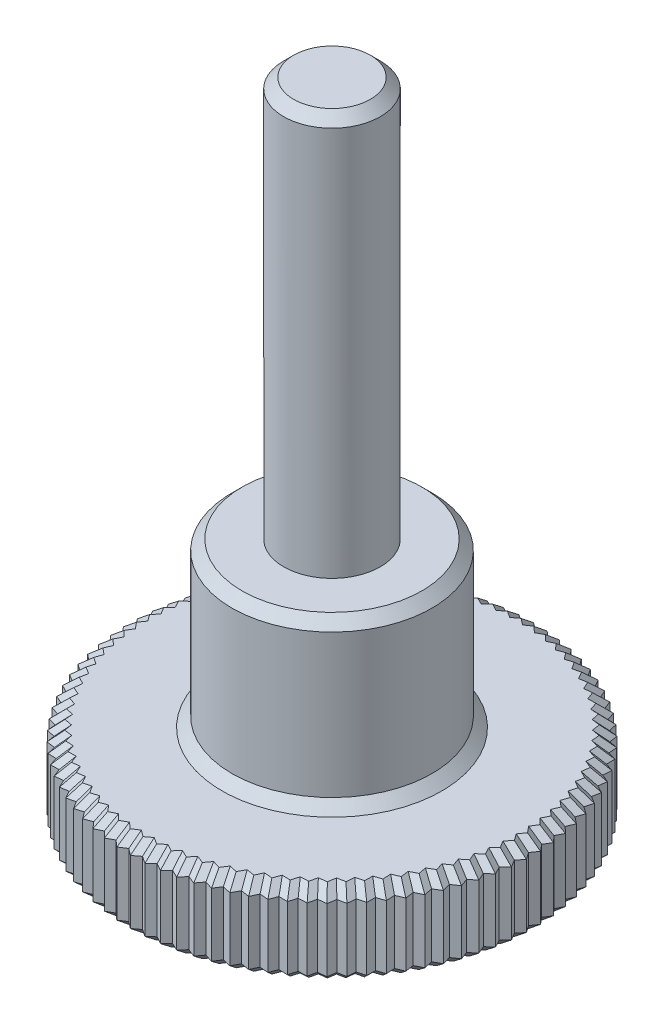
SolidWorks part; units mm, degrees
material "AISI 1020"
ref_plane "Front Plane" through (0, 0, 0) normal (0, 0, 1) x (1, 0, 0)
ref_plane "Top Plane" through (0, 0, 0) normal (0, 1, 0) x (1, 0, 0)
ref_plane "Right Plane" through (0, 0, 0) normal (1, 0, 0) x (0, 0, -1)
sketch "Sketch1" plane through (0, 0, 0) normal (0, 1, 0) x (1, 0, 0)
  line L0 (0, 0) -> (0, 6.05) construction
  line L1 (0, 6.05) -> (0.2058, 5.8938)
  line L2 (0.422, 6.0353) -> (0.2058, 5.8938)
  line L3 (0.2111, 6.0463) -> (0, 0) construction
  line L4 (0.422, 6.0353) -> (0.6164, 5.8651)
  line L5 (0.842, 5.9911) -> (0.6164, 5.8651)
  line L6 (0.842, 5.9911) -> (1.0241, 5.8078)
  line L7 (1.2579, 5.9178) -> (1.0241, 5.8078)
  line L8 (1.2579, 5.9178) -> (1.4267, 5.7222)
  line L9 (1.6676, 5.8156) -> (1.4267, 5.7222)
  line L10 (1.6676, 5.8156) -> (1.8224, 5.6088)
  line L11 (2.0692, 5.6851) -> (1.8224, 5.6088)
  line L12 (2.0692, 5.6851) -> (2.2092, 5.468)
  line L13 (2.4608, 5.527) -> (2.2092, 5.468)
  line L14 (2.4608, 5.527) -> (2.5852, 5.3005)
  line L15 (2.8403, 5.3418) -> (2.5852, 5.3005)
  line L16 (2.8403, 5.3418) -> (2.9487, 5.1073)
  line L17 (3.206, 5.1307) -> (2.9487, 5.1073)
  line L18 (3.206, 5.1307) -> (3.2978, 4.8892)
  line L19 (3.5561, 4.8946) -> (3.2978, 4.8892)
  line L20 (3.5561, 4.8946) -> (3.6308, 4.6472)
  line L21 (3.8889, 4.6346) -> (3.6308, 4.6472)
  line L22 (3.8889, 4.6346) -> (3.9461, 4.3826)
  line L23 (4.2027, 4.352) -> (3.9461, 4.3826)
  line L24 (4.2027, 4.352) -> (4.2422, 4.0967)
  line L25 (4.496, 4.0482) -> (4.2422, 4.0967)
  line L26 (4.496, 4.0482) -> (4.5177, 3.7908)
  line L27 (4.7675, 3.7248) -> (4.5177, 3.7908)
  line L28 (4.7675, 3.7248) -> (4.7711, 3.4664)
  line L29 (5.0157, 3.3831) -> (4.7711, 3.4664)
  line L30 (5.0157, 3.3831) -> (5.0013, 3.1251)
  line L31 (5.2395, 3.025) -> (5.0013, 3.1251)
  line L32 (5.2395, 3.025) -> (5.2071, 2.7687)
  line L33 (5.4377, 2.6521) -> (5.2071, 2.7687)
  line L34 (5.4377, 2.6521) -> (5.3875, 2.3987)
  line L35 (5.6095, 2.2664) -> (5.3875, 2.3987)
  line L36 (5.6095, 2.2664) -> (5.5417, 2.017)
  line L37 (5.7539, 1.8696) -> (5.5417, 2.017)
  line L38 (5.7539, 1.8696) -> (5.6689, 1.6255)
  line L39 (5.8703, 1.4636) -> (5.6689, 1.6255)
  line L40 (5.8703, 1.4636) -> (5.7685, 1.2261)
  line L41 (5.9581, 1.0506) -> (5.7685, 1.2261)
  line L42 (5.9581, 1.0506) -> (5.84, 0.8208)
  line L43 (6.0169, 0.6324) -> (5.84, 0.8208)
  line L44 (6.0169, 0.6324) -> (5.883, 0.4114)
  line L45 (6.0463, 0.2111) -> (5.883, 0.4114)
  line L46 (6.0463, 0.2111) -> (5.8974, 0)
  line L47 (6.0463, -0.2111) -> (5.8974, 0)
  line L48 (6.0463, -0.2111) -> (5.883, -0.4114)
  line L49 (6.0169, -0.6324) -> (5.883, -0.4114)
  line L50 (6.0169, -0.6324) -> (5.84, -0.8208)
  line L51 (5.9581, -1.0506) -> (5.84, -0.8208)
  line L52 (5.9581, -1.0506) -> (5.7685, -1.2261)
  line L53 (5.8703, -1.4636) -> (5.7685, -1.2261)
  line L54 (5.8703, -1.4636) -> (5.6689, -1.6255)
  line L55 (5.7539, -1.8696) -> (5.6689, -1.6255)
  line L56 (5.7539, -1.8696) -> (5.5417, -2.017)
  line L57 (5.6095, -2.2664) -> (5.5417, -2.017)
  line L58 (5.6095, -2.2664) -> (5.3875, -2.3987)
  line L59 (5.4377, -2.6521) -> (5.3875, -2.3987)
  line L60 (5.4377, -2.6521) -> (5.2071, -2.7687)
  line L61 (5.2395, -3.025) -> (5.2071, -2.7687)
  line L62 (5.2395, -3.025) -> (5.0013, -3.1251)
  line L63 (5.0157, -3.3831) -> (5.0013, -3.1251)
  line L64 (5.0157, -3.3831) -> (4.7711, -3.4664)
  line L65 (4.7675, -3.7248) -> (4.7711, -3.4664)
  line L66 (4.7675, -3.7248) -> (4.5177, -3.7908)
  line L67 (4.496, -4.0482) -> (4.5177, -3.7908)
  line L68 (4.496, -4.0482) -> (4.2422, -4.0967)
  line L69 (4.2027, -4.352) -> (4.2422, -4.0967)
  line L70 (4.2027, -4.352) -> (3.9461, -4.3826)
  line L71 (3.8889, -4.6346) -> (3.9461, -4.3826)
  line L72 (3.8889, -4.6346) -> (3.6308, -4.6472)
  line L73 (3.5561, -4.8946) -> (3.6308, -4.6472)
  line L74 (3.5561, -4.8946) -> (3.2978, -4.8892)
  line L75 (3.206, -5.1307) -> (3.2978, -4.8892)
  line L76 (3.206, -5.1307) -> (2.9487, -5.1073)
  line L77 (2.8403, -5.3418) -> (2.9487, -5.1073)
  line L78 (2.8403, -5.3418) -> (2.5852, -5.3005)
  line L79 (2.4608, -5.527) -> (2.5852, -5.3005)
  line L80 (2.4608, -5.527) -> (2.2092, -5.468)
  line L81 (2.0692, -5.6851) -> (2.2092, -5.468)
  line L82 (2.0692, -5.6851) -> (1.8224, -5.6088)
  line L83 (1.6676, -5.8156) -> (1.8224, -5.6088)
  line L84 (1.6676, -5.8156) -> (1.4267, -5.7222)
  line L85 (1.2579, -5.9178) -> (1.4267, -5.7222)
  line L86 (1.2579, -5.9178) -> (1.0241, -5.8078)
  line L87 (0.842, -5.9911) -> (1.0241, -5.8078)
  line L88 (0.842, -5.9911) -> (0.6164, -5.8651)
  line L89 (0.422, -6.0353) -> (0.6164, -5.8651)
  line L90 (0.422, -6.0353) -> (0.2058, -5.8938)
  line L91 (0, -6.05) -> (0.2058, -5.8938)
  line L92 (0, -6.05) -> (-0.2058, -5.8938)
  line L93 (-0.422, -6.0353) -> (-0.2058, -5.8938)
  line L94 (-0.422, -6.0353) -> (-0.6164, -5.8651)
  line L95 (-0.842, -5.9911) -> (-0.6164, -5.8651)
  line L96 (-0.842, -5.9911) -> (-1.0241, -5.8078)
  line L97 (-1.2579, -5.9178) -> (-1.0241, -5.8078)
  line L98 (-1.2579, -5.9178) -> (-1.4267, -5.7222)
  line L99 (-1.6676, -5.8156) -> (-1.4267, -5.7222)
  line L100 (-1.6676, -5.8156) -> (-1.8224, -5.6088)
  line L101 (-2.0692, -5.6851) -> (-1.8224, -5.6088)
  line L102 (-2.0692, -5.6851) -> (-2.2092, -5.468)
  line L103 (-2.4608, -5.527) -> (-2.2092, -5.468)
  line L104 (-2.4608, -5.527) -> (-2.5852, -5.3005)
  line L105 (-2.8403, -5.3418) -> (-2.5852, -5.3005)
  line L106 (-2.8403, -5.3418) -> (-2.9487, -5.1073)
  line L107 (-3.206, -5.1307) -> (-2.9487, -5.1073)
  line L108 (-3.206, -5.1307) -> (-3.2978, -4.8892)
  line L109 (-3.5561, -4.8946) -> (-3.2978, -4.8892)
  line L110 (-3.5561, -4.8946) -> (-3.6308, -4.6472)
  line L111 (-3.8889, -4.6346) -> (-3.6308, -4.6472)
  line L112 (-3.8889, -4.6346) -> (-3.9461, -4.3826)
  line L113 (-4.2027, -4.352) -> (-3.9461, -4.3826)
  line L114 (-4.2027, -4.352) -> (-4.2422, -4.0967)
  line L115 (-4.496, -4.0482) -> (-4.2422, -4.0967)
  line L116 (-4.496, -4.0482) -> (-4.5177, -3.7908)
  line L117 (-4.7675, -3.7248) -> (-4.5177, -3.7908)
  line L118 (-4.7675, -3.7248) -> (-4.7711, -3.4664)
  line L119 (-5.0157, -3.3831) -> (-4.7711, -3.4664)
  line L120 (-5.0157, -3.3831) -> (-5.0013, -3.1251)
  line L121 (-5.2395, -3.025) -> (-5.0013, -3.1251)
  line L122 (-5.2395, -3.025) -> (-5.2071, -2.7687)
  line L123 (-5.4377, -2.6521) -> (-5.2071, -2.7687)
  line L124 (-5.4377, -2.6521) -> (-5.3875, -2.3987)
  line L125 (-5.6095, -2.2664) -> (-5.3875, -2.3987)
  line L126 (-5.6095, -2.2664) -> (-5.5417, -2.017)
  line L127 (-5.7539, -1.8696) -> (-5.5417, -2.017)
  line L128 (-5.7539, -1.8696) -> (-5.6689, -1.6255)
  line L129 (-5.8703, -1.4636) -> (-5.6689, -1.6255)
  line L130 (-5.8703, -1.4636) -> (-5.7685, -1.2261)
  line L131 (-5.9581, -1.0506) -> (-5.7685, -1.2261)
  line L132 (-5.9581, -1.0506) -> (-5.84, -0.8208)
  line L133 (-6.0169, -0.6324) -> (-5.84, -0.8208)
  line L134 (-6.0169, -0.6324) -> (-5.883, -0.4114)
  line L135 (-6.0463, -0.2111) -> (-5.883, -0.4114)
  line L136 (-6.0463, -0.2111) -> (-5.8974, 0)
  line L137 (-6.0463, 0.2111) -> (-5.8974, 0)
  line L138 (-6.0463, 0.2111) -> (-5.883, 0.4114)
  line L139 (-6.0169, 0.6324) -> (-5.883, 0.4114)
  line L140 (-6.0169, 0.6324) -> (-5.84, 0.8208)
  line L141 (-5.9581, 1.0506) -> (-5.84, 0.8208)
  line L142 (-5.9581, 1.0506) -> (-5.7685, 1.2261)
  line L143 (-5.8703, 1.4636) -> (-5.7685, 1.2261)
  line L144 (-5.8703, 1.4636) -> (-5.6689, 1.6255)
  line L145 (-5.7539, 1.8696) -> (-5.6689, 1.6255)
  line L146 (-5.7539, 1.8696) -> (-5.5417, 2.017)
  line L147 (-5.6095, 2.2664) -> (-5.5417, 2.017)
  line L148 (-5.6095, 2.2664) -> (-5.3875, 2.3987)
  line L149 (-5.4377, 2.6521) -> (-5.3875, 2.3987)
  line L150 (-5.4377, 2.6521) -> (-5.2071, 2.7687)
  line L151 (-5.2395, 3.025) -> (-5.2071, 2.7687)
  line L152 (-5.2395, 3.025) -> (-5.0013, 3.1251)
  line L153 (-5.0157, 3.3831) -> (-5.0013, 3.1251)
  line L154 (-5.0157, 3.3831) -> (-4.7711, 3.4664)
  line L155 (-4.7675, 3.7248) -> (-4.7711, 3.4664)
  line L156 (-4.7675, 3.7248) -> (-4.5177, 3.7908)
  line L157 (-4.496, 4.0482) -> (-4.5177, 3.7908)
  line L158 (-4.496, 4.0482) -> (-4.2422, 4.0967)
  line L159 (-4.2027, 4.352) -> (-4.2422, 4.0967)
  line L160 (-4.2027, 4.352) -> (-3.9461, 4.3826)
  line L161 (-3.8889, 4.6346) -> (-3.9461, 4.3826)
  line L162 (-3.8889, 4.6346) -> (-3.6308, 4.6472)
  line L163 (-3.5561, 4.8946) -> (-3.6308, 4.6472)
  line L164 (-3.5561, 4.8946) -> (-3.2978, 4.8892)
  line L165 (-3.206, 5.1307) -> (-3.2978, 4.8892)
  line L166 (-3.206, 5.1307) -> (-2.9487, 5.1073)
  line L167 (-2.8403, 5.3418) -> (-2.9487, 5.1073)
  line L168 (-2.8403, 5.3418) -> (-2.5852, 5.3005)
  line L169 (-2.4608, 5.527) -> (-2.5852, 5.3005)
  line L170 (-2.4608, 5.527) -> (-2.2092, 5.468)
  line L171 (-2.0692, 5.6851) -> (-2.2092, 5.468)
  line L172 (-2.0692, 5.6851) -> (-1.8224, 5.6088)
  line L173 (-1.6676, 5.8156) -> (-1.8224, 5.6088)
  line L174 (-1.6676, 5.8156) -> (-1.4267, 5.7222)
  line L175 (-1.2579, 5.9178) -> (-1.4267, 5.7222)
  line L176 (-1.2579, 5.9178) -> (-1.0241, 5.8078)
  line L177 (-0.842, 5.9911) -> (-1.0241, 5.8078)
  line L178 (-0.842, 5.9911) -> (-0.6164, 5.8651)
  line L179 (-0.422, 6.0353) -> (-0.6164, 5.8651)
  line L180 (-0.422, 6.0353) -> (-0.2058, 5.8938)
  line L181 (0, 6.05) -> (-0.2058, 5.8938)
  circle A0 centre (0, 0) radius 6.05
  dimension "D1" = 12.1
  dimension "D2" = 2
  dimension "D3" = 90
extrude "Extrude1" add sketch "Sketch1" along normal blind 2.5 contours L1 L181 L180 L179 L178 L177 L176 L175 L174 L173 L172 L171 L170 L169 L168 L167 L166 L165 L164 L163 L162 L161 L160 L159 L158 L157 L156 L155 L154 L153 L152 L151 L150 L149 L148 L147 L146 L145 L144 L143 L142 L141 L140 L139 L138 L137 L136 L135 L134 L133 L132
sketch "Sketch2" plane through (0, 2.5, 0) normal (0, 1, 0) x (1, 0, 0)
  circle A0 centre (0, 0) radius 3
  dimension "D1" = 6
extrude "Extrude2" add sketch "Sketch2" along normal blind 4.9
sketch "Sketch3" plane through (0, 7.4, 0) normal (0, 1, 0) x (1, 0, 0)
  circle A0 centre (0, 0) radius 1.45
  dimension "D1" = 2.9
extrude "Extrude3" add sketch "Sketch3" along normal blind 12
cosmetic thread "Cosmetic Thread1" parameters "D2"=1.993
chamfer "Chamfer1" distance 0.3 angle 45 363 edges at (0.3139, 2.5, -5.9645) (0.5192, 2.5, -5.9502) (0.7292, 2.5, -5.9281) (0.933, 2.5, -5.8995) (1.141, 2.5, -5.8628) (1.3423, 2.5, -5.82) (1.5472, 2.5, -5.7689) (1.745, 2.5, -5.7122) (1.9458, 2.5, -5.6469) (2.1392, 2.5, -5.5766) (2.335, 2.5, -5.4975) (2.523, 2.5, -5.4137) (2.7128, 2.5, -5.3212) (2.8945, 2.5, -5.2246) (3.0774, 2.5, -5.119) (3.2519, 2.5, -5.0099) (3.4269, 2.5, -4.8919) (3.5935, 2.5, -4.7709) (3.7598, 2.5, -4.6409) (3.9175, 2.5, -4.5086) (4.0744, 2.5, -4.3673) (4.2225, 2.5, -4.2243) (4.3691, 2.5, -4.0725) (4.5068, 2.5, -3.9195) (4.6426, 2.5, -3.7578) (4.7693, 2.5, -3.5956) (4.8934, 2.5, -3.4248) (5.0085, 2.5, -3.2541) (5.1204, 2.5, -3.0751) (5.2233, 2.5, -2.8968) (5.3224, 2.5, -2.7104) (5.4126, 2.5, -2.5254) (5.4985, 2.5, -2.3325) (5.5756, 2.5, -2.1417) (5.6478, 2.5, -1.9433) (5.7114, 2.5, -1.7475) (5.7696, 2.5, -1.5446) (5.8194, 2.5, -1.3449) (5.8633, 2.5, -1.1384) (5.899, 2.5, -0.9357) (5.9284, 2.5, -0.7266) (5.9499, 2.5, -0.5219) (5.9647, 2.5, -0.3113) (5.9719, 2.5, -0.1056) (5.9719, 2.5, 0.1056) (5.9647, 2.5, 0.3113) (5.9499, 2.5, 0.5219) (5.9284, 2.5, 0.7266) (5.899, 2.5, 0.9357) (5.8633, 2.5, 1.1384) (5.8194, 2.5, 1.3449) (5.7696, 2.5, 1.5446) (5.7114, 2.5, 1.7475) (5.6478, 2.5, 1.9433) (5.5756, 2.5, 2.1417) (5.4985, 2.5, 2.3325) (5.4126, 2.5, 2.5254) (5.3224, 2.5, 2.7104) (5.2233, 2.5, 2.8968) (5.1204, 2.5, 3.0751) (5.0085, 2.5, 3.2541) (4.8934, 2.5, 3.4248) (4.7693, 2.5, 3.5956) (4.6426, 2.5, 3.7578) (4.5068, 2.5, 3.9195) (4.3691, 2.5, 4.0725) (4.2225, 2.5, 4.2243) (4.0744, 2.5, 4.3673) (3.9175, 2.5, 4.5086) (3.7598, 2.5, 4.6409) (3.5935, 2.5, 4.7709) (3.4269, 2.5, 4.8919) (3.2519, 2.5, 5.0099) (3.0774, 2.5, 5.119) (2.8945, 2.5, 5.2246) (2.7128, 2.5, 5.3212) (2.523, 2.5, 5.4137) (2.335, 2.5, 5.4975) (2.1392, 2.5, 5.5766) (1.9458, 2.5, 5.6469) (1.745, 2.5, 5.7122) (1.5472, 2.5, 5.7689) (1.3423, 2.5, 5.82) (1.141, 2.5, 5.8628) (0.933, 2.5, 5.8995) (0.7292, 2.5, 5.9281) (0.5192, 2.5, 5.9502) (0.3139, 2.5, 5.9645) (0.1029, 2.5, 5.9719) (-0.1029, 2.5, 5.9719) (-0.3139, 2.5, 5.9645) (-0.5192, 2.5, 5.9502) (-0.7292, 2.5, 5.9281) (-0.933, 2.5, 5.8995) (-1.141, 2.5, 5.8628) (-1.3423, 2.5, 5.82) (-1.5472, 2.5, 5.7689) (-1.745, 2.5, 5.7122) (-1.9458, 2.5, 5.6469) (-2.1392, 2.5, 5.5766) (-2.335, 2.5, 5.4975) (-2.523, 2.5, 5.4137) (-2.7128, 2.5, 5.3212) (-2.8945, 2.5, 5.2246) (-3.0774, 2.5, 5.119) (-3.2519, 2.5, 5.0099) (-3.4269, 2.5, 4.8919) (-3.5935, 2.5, 4.7709) (-3.7598, 2.5, 4.6409) (-3.9175, 2.5, 4.5086) (-4.0744, 2.5, 4.3673) (-4.2225, 2.5, 4.2243) (-4.3691, 2.5, 4.0725) (-4.5068, 2.5, 3.9195) (-4.6426, 2.5, 3.7578) (-4.7693, 2.5, 3.5956) (-4.8934, 2.5, 3.4248) (-5.0085, 2.5, 3.2541) (-5.1204, 2.5, 3.0751) (-5.2233, 2.5, 2.8968) (-5.3224, 2.5, 2.7104) (-5.4126, 2.5, 2.5254) (-5.4985, 2.5, 2.3325) (-5.5756, 2.5, 2.1417) (-5.6478, 2.5, 1.9433) (-5.7114, 2.5, 1.7475) (-5.7696, 2.5, 1.5446) (-5.8194, 2.5, 1.3449) (-5.8633, 2.5, 1.1384) (-5.899, 2.5, 0.9357) (-5.9284, 2.5, 0.7266) (-5.9499, 2.5, 0.5219) (-5.9647, 2.5, 0.3113) (-5.9719, 2.5, 0.1056) (-5.9719, 2.5, -0.1056) (-5.9647, 2.5, -0.3113) (-5.9499, 2.5, -0.5219) (-5.9284, 2.5, -0.7266) (-5.899, 2.5, -0.9357) (-5.8633, 2.5, -1.1384) (-5.8194, 2.5, -1.3449) (-5.7696, 2.5, -1.5446) (-5.7114, 2.5, -1.7475) (-5.6478, 2.5, -1.9433) (-5.5756, 2.5, -2.1417) (-5.4985, 2.5, -2.3325) (-5.4126, 2.5, -2.5254) (-5.3224, 2.5, -2.7104) (-5.2233, 2.5, -2.8968) (-5.1204, 2.5, -3.0751) (-5.0085, 2.5, -3.2541) (-4.8934, 2.5, -3.4248) (-4.7693, 2.5, -3.5956) (-4.6426, 2.5, -3.7578) (-4.5068, 2.5, -3.9195) (-4.3691, 2.5, -4.0725) (-4.2225, 2.5, -4.2243) (-4.0744, 2.5, -4.3673) (-3.9175, 2.5, -4.5086) (-3.7598, 2.5, -4.6409) (-3.5935, 2.5, -4.7709) (-3.4269, 2.5, -4.8919) (-3.2519, 2.5, -5.0099) (-3.0774, 2.5, -5.119) (-2.8945, 2.5, -5.2246) (-2.7128, 2.5, -5.3212) (-2.523, 2.5, -5.4137) (-2.335, 2.5, -5.4975) (-2.1392, 2.5, -5.5766) (-1.9458, 2.5, -5.6469) (-1.745, 2.5, -5.7122) (-1.5472, 2.5, -5.7689) (-1.3423, 2.5, -5.82) (-1.141, 2.5, -5.8628) (-0.933, 2.5, -5.8995) (-0.7292, 2.5, -5.9281) (-0.5192, 2.5, -5.9502) (-0.3139, 2.5, -5.9645) (-0.1029, 2.5, -5.9719) (0.1029, 2.5, -5.9719) (0, 2.5, 3) (-0.1029, 0, -5.9719) (-0.3139, 0, -5.9645) (-0.5192, 0, -5.9502) (-0.7292, 0, -5.9281) (-0.933, 0, -5.8995) (-1.141, 0, -5.8628) (-1.3423, 0, -5.82) (-1.5472, 0, -5.7689) (-1.745, 0, -5.7122) (-1.9458, 0, -5.6469) (-2.1392, 0, -5.5766) (-2.335, 0, -5.4975) (-2.523, 0, -5.4137) (-2.7128, 0, -5.3212) (-2.8945, 0, -5.2246) (-3.0774, 0, -5.119) (-3.2519, 0, -5.0099) (-3.4269, 0, -4.8919) (-3.5935, 0, -4.7709) (-3.7598, 0, -4.6409) (-3.9175, 0, -4.5086) (-4.0744, 0, -4.3673) (-4.2225, 0, -4.2243) (-4.3691, 0, -4.0725) (-4.5068, 0, -3.9195) (-4.6426, 0, -3.7578) (-4.7693, 0, -3.5956) (-4.8934, 0, -3.4248) (-5.0085, 0, -3.2541) (-5.1204, 0, -3.0751) (-5.2233, 0, -2.8968) (-5.3224, 0, -2.7104) (-5.4126, 0, -2.5254) (-5.4985, 0, -2.3325) (-5.5756, 0, -2.1417) (-5.6478, 0, -1.9433) (-5.7114, 0, -1.7475) (-5.7696, 0, -1.5446) (-5.8194, 0, -1.3449) (-5.8633, 0, -1.1384) (-5.899, 0, -0.9357) (-5.9284, 0, -0.7266) (-5.9499, 0, -0.5219) (-5.9647, 0, -0.3113) (-5.9719, 0, -0.1056) (-5.9719, 0, 0.1056) (-5.9647, 0, 0.3113) (-5.9499, 0, 0.5219) (-5.9284, 0, 0.7266) (-5.899, 0, 0.9357) (-5.8633, 0, 1.1384) (-5.8194, 0, 1.3449) (-5.7696, 0, 1.5446) (-5.7114, 0, 1.7475) (-5.6478, 0, 1.9433) (-5.5756, 0, 2.1417) (-5.4985, 0, 2.3325) (-5.4126, 0, 2.5254) (-5.3224, 0, 2.7104) (-5.2233, 0, 2.8968) (-5.1204, 0, 3.0751) (-5.0085, 0, 3.2541) (-4.8934, 0, 3.4248) (-4.7693, 0, 3.5956) (-4.6426, 0, 3.7578) (-4.5068, 0, 3.9195) (-4.3691, 0, 4.0725) (-4.2225, 0, 4.2243) (-4.0744, 0, 4.3673) (-3.9175, 0, 4.5086) (-3.7598, 0, 4.6409) (-3.5935, 0, 4.7709) (-3.4269, 0, 4.8919) (-3.2519, 0, 5.0099) (-3.0774, 0, 5.119) (-2.8945, 0, 5.2246) (-2.7128, 0, 5.3212) (-2.523, 0, 5.4137) (-2.335, 0, 5.4975) (-2.1392, 0, 5.5766) (-1.9458, 0, 5.6469) (-1.745, 0, 5.7122) (-1.5472, 0, 5.7689) (-1.3423, 0, 5.82) (-1.141, 0, 5.8628) (-0.933, 0, 5.8995) (-0.7292, 0, 5.9281) (-0.5192, 0, 5.9502) (-0.3139, 0, 5.9645) (-0.1029, 0, 5.9719) (0.1029, 0, 5.9719) (0.3139, 0, 5.9645) (0.5192, 0, 5.9502) (0.7292, 0, 5.9281) (0.933, 0, 5.8995) (1.141, 0, 5.8628) (1.3423, 0, 5.82) (1.5472, 0, 5.7689) (1.745, 0, 5.7122) (1.9458, 0, 5.6469) (2.1392, 0, 5.5766) (2.335, 0, 5.4975) (2.523, 0, 5.4137) (2.7128, 0, 5.3212) (2.8945, 0, 5.2246) (3.0774, 0, 5.119) (3.2519, 0, 5.0099) (3.4269, 0, 4.8919) (3.5935, 0, 4.7709) (3.7598, 0, 4.6409) (3.9175, 0, 4.5086) (4.0744, 0, 4.3673) (4.2225, 0, 4.2243) (4.3691, 0, 4.0725) (4.5068, 0, 3.9195) (4.6426, 0, 3.7578) (4.7693, 0, 3.5956) (4.8934, 0, 3.4248) (5.0085, 0, 3.2541) (5.1204, 0, 3.0751) (5.2233, 0, 2.8968) (5.3224, 0, 2.7104) (5.4126, 0, 2.5254) (5.4985, 0, 2.3325) (5.5756, 0, 2.1417) (5.6478, 0, 1.9433) (5.7114, 0, 1.7475) (5.7696, 0, 1.5446) (5.8194, 0, 1.3449) (5.8633, 0, 1.1384) (5.899, 0, 0.9357) (5.9284, 0, 0.7266) (5.9499, 0, 0.5219) (5.9647, 0, 0.3113) (5.9719, 0, 0.1056) (5.9719, 0, -0.1056) (5.9647, 0, -0.3113) (5.9499, 0, -0.5219) (5.9284, 0, -0.7266) (5.899, 0, -0.9357) (5.8633, 0, -1.1384) (5.8194, 0, -1.3449) (5.7696, 0, -1.5446) (5.7114, 0, -1.7475) (5.6478, 0, -1.9433) (5.5756, 0, -2.1417) (5.4985, 0, -2.3325) (5.4126, 0, -2.5254) (5.3224, 0, -2.7104) (5.2233, 0, -2.8968) (5.1204, 0, -3.0751) (5.0085, 0, -3.2541) (4.8934, 0, -3.4248) (4.7693, 0, -3.5956) (4.6426, 0, -3.7578) (4.5068, 0, -3.9195) (4.3691, 0, -4.0725) (4.2225, 0, -4.2243) (4.0744, 0, -4.3673) (3.9175, 0, -4.5086) (3.7598, 0, -4.6409) (3.5935, 0, -4.7709) (3.4269, 0, -4.8919) (3.2519, 0, -5.0099) (3.0774, 0, -5.119) (2.8945, 0, -5.2246) (2.7128, 0, -5.3212) (2.523, 0, -5.4137) (2.335, 0, -5.4975) (2.1392, 0, -5.5766) (1.9458, 0, -5.6469) (1.745, 0, -5.7122) (1.5472, 0, -5.7689) (1.3423, 0, -5.82) (1.141, 0, -5.8628) (0.933, 0, -5.8995) (0.7292, 0, -5.9281) (0.5192, 0, -5.9502) (0.3139, 0, -5.9645) (0.1029, 0, -5.9719) (0, 19.4, 1.45) (0, 7.4, 3)
